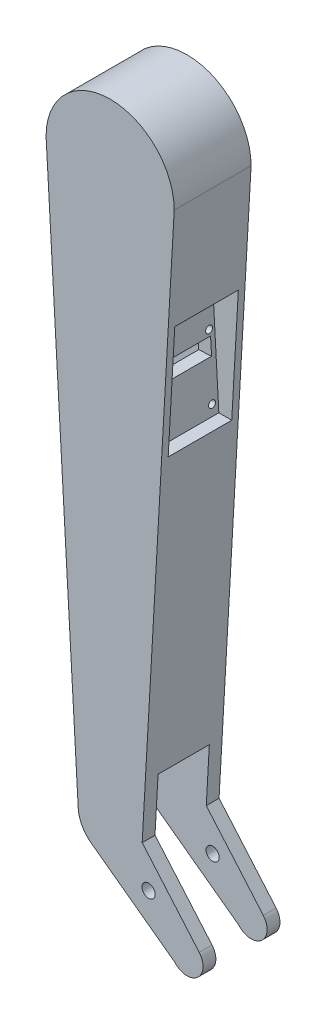
SolidWorks part; units mm, degrees
ref_plane "Plan de face" through (0, 0, 0) normal (0, 0, 1) x (1, 0, 0)
ref_plane "Plan de dessus" through (0, 0, 0) normal (0, 1, 0) x (1, 0, 0)
ref_plane "Plan de droite" through (0, 0, 0) normal (1, 0, 0) x (0, 0, -1)
sketch "Esquisse1" plane through (0, 0, 0) normal (0, 0, 1) x (1, 0, 0)
  line L0 (0, -110) -> (0, 110) construction
  line L1 (-25, 110) -> (-12.5, -110)
  line L2 (0, -110) -> (30, -140) construction
  line L3 (25, 110) -> (12.5, -110)
  line L4 (12.5, -110) -> (34.7438, -135.9307)
  line L5 (34.7438, -135.9307) -> (48.7, -152.2003) construction
  line L6 (34.7438, -135.9307) -> (25.2562, -144.0693) construction
  line L7 (25.2562, -144.0693) -> (-7.4015, -120.0731)
  line L8 (-7.4015, -120.0731) -> (-23.8801, -107.9651) construction
  circle A1 centre (0, 110) radius 25
  circle A6 centre (0, -110) radius 12.5
  circle A7 centre (30, -140) radius 6.25
  circle A8 centre (15, -125) radius 2.575
  point P5 (0, 0)
  point P8 (0, -110)
  dimension "D1" = 25
  dimension "D2" = 50
  dimension "D3" = 220
  dimension "D4" = 250
  dimension "D6" = 12.5
  dimension "D8" = 5.15
  dimension "D5" = 135
  dimension "D7" = 42.4264
extrude "Boss.-Extru.1" add sketch "Esquisse1" along normal mid plane 30 contours A6 L3 A1 L1 | A6 | A7 L4 A6 L7 | A7 | L3 A1 L1 region at (0, 110.0001, 0) region at (0, 4.1251, 0) region at (0, -110, 0) region at (23.2106, -123.3182, 0) region at (30, -140, 0)
sketch "Esquisse2" plane through (0, 0, 0) normal (1, 0, 0) x (0, 0, -1)
  line L0 (-69.6928, 57.9096) -> (69.6928, 57.9096) construction
  line L1 (0, -135.9307) -> (0, -146.25) construction
  line L2 (0, 156.2152) -> (0, -156.2152) construction
  line L3 (-15, -110) -> (15, -110) construction
  line L4 (-12.4, 22.8096) -> (12.4, 22.8096)
  line L5 (-12.4, 22.8096) -> (-12.4, 68.1096)
  line L6 (-12.4, 68.1096) -> (12.4, 68.1096)
  line L7 (12.4, 22.8096) -> (12.4, 68.1096)
  line L8 (-12.4, 22.8096) -> (12.4, 68.1096) construction
  line L9 (-12.4, 68.1096) -> (12.4, 22.8096) construction
  line L10 (10, -190) -> (-10, -190)
  line L11 (10, -190) -> (10, -110)
  line L12 (10, -110) -> (-10, -110)
  line L13 (-10, -190) -> (-10, -110)
  line L14 (10, -190) -> (-10, -110) construction
  line L15 (10, -110) -> (-10, -190) construction
  line L16 (-15, -135.9307) -> (15, -135.9307) construction
  line L17 (-15, -146.25) -> (15, -146.25) construction
  point P3 (0, 57.9096)
  point P6 (0, 45.4596)
  point P13 (0, -150)
  point P25 (0, -141.0904)
  dimension "D1" = 45.3
  dimension "D2" = 24.8
  dimension "D3" = 10.2
  dimension "D4" = 20
  dimension "D5" = 80
  dimension "D6" = 199
extrude "Enlèv. mat.-Extru.1" cut sketch "Esquisse2" against normal through all both and the other way through all
ref_plane "Plan1" through (11.262, 0.6399, 0) normal (-0.9984, -0.0567, 0) x (0, 0, 1)
sketch "Esquisse3" plane through (11.262, 0.6399, 0) normal (-0.9984, -0.0567, 0) x (0, 0, 1)
  line L14 (10.8386, 48.0555) -> (-10.6617, 48.0555)
  line L15 (10.8386, 48.0555) -> (10.8386, 41.3805)
  line L16 (10.8386, 41.3805) -> (-10.6617, 41.3805)
  line L17 (-10.6617, 48.0555) -> (-10.6617, 41.3805)
  line L25 (-12.4, 74.2831) -> (12.4, 74.2831)
  line L26 (-12.4, 74.2831) -> (-12.4, 18.9101)
  line L27 (-12.4, 18.9101) -> (12.4, 18.9101)
  line L28 (12.4, 74.2831) -> (12.4, 18.9101)
  line L32 (-12.4, 69.2831) -> (12.4, 69.2831) construction
  line L33 (12.4, 23.9101) -> (-12.4, 23.9101) construction
  line L35 (12.4, 69.2831) -> (12.4, 66.7168) construction
  line L36 (-12.4, 21.6358) -> (-12.4, 66.7168) construction
  circle A6 centre (-9.9617, 25.9555) radius 1.35
  circle A7 centre (10.0383, 25.9555) radius 1.35
  circle A10 centre (-10.2117, 50.4055) radius 1.35
  circle A11 centre (10.2883, 50.4055) radius 1.35
  point P24 (10.0383, 74.9854)
  dimension "D1" = 5
  dimension "D2" = 2.7
  dimension "D3" = 5
extrude "Boss.-Extru.2" add sketch "Esquisse3" against normal blind 5
chamfer "Chanfrein1" distance 20 angle 45 1 edges at (12.5, -110, 0) first distance on face at (0, -110, 0)
ref_plane "Plan de rotation" through (15, 0, 0) normal (1, 0, 0) x (0, 0, -1)
